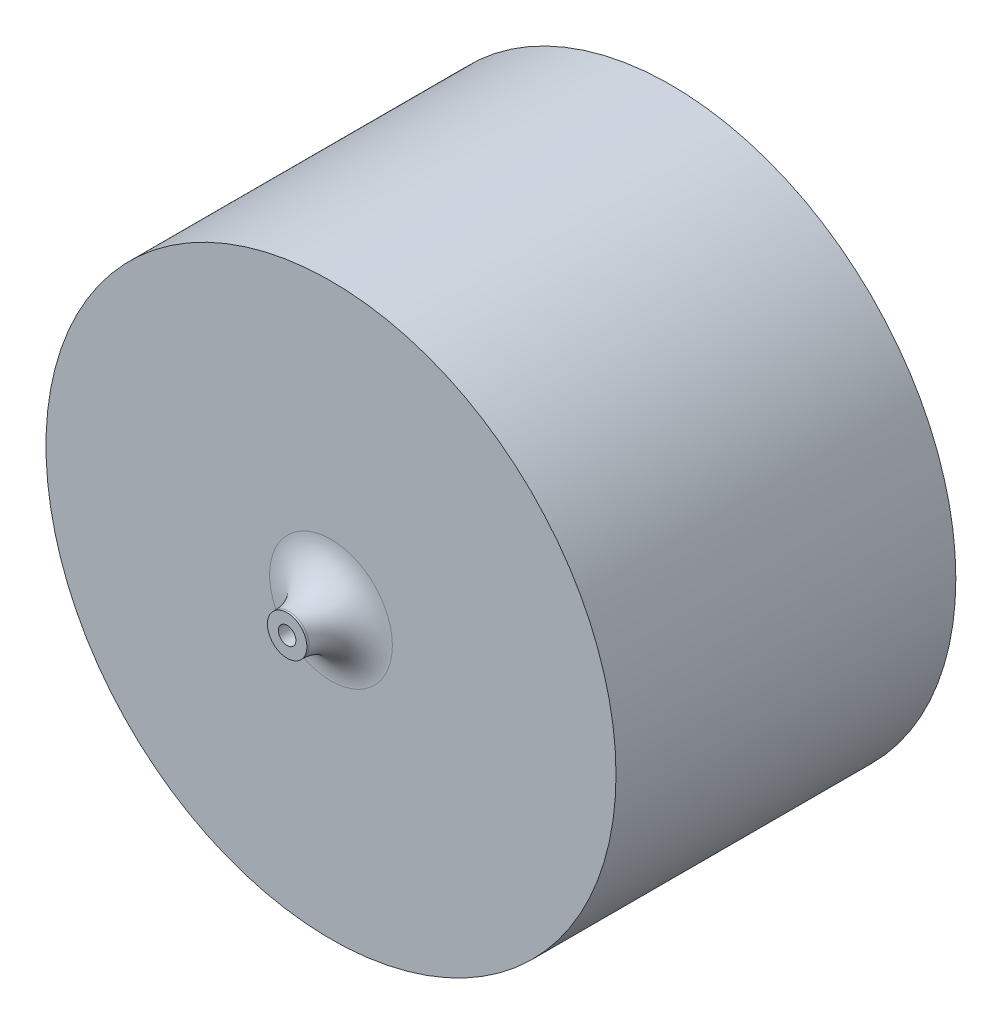
SolidWorks part; units mm, degrees
ref_plane "Front Plane" through (0, 0, 0) normal (0, 0, 1) x (1, 0, 0)
ref_plane "Top Plane" through (0, 0, 0) normal (0, 1, 0) x (1, 0, 0)
ref_plane "Right Plane" through (0, 0, 0) normal (1, 0, 0) x (0, 0, -1)
sketch "Sketch1" plane through (0, 0, 0) normal (1, 0, 0) x (0, 0, -1)
  line L0 (0, 0) -> (46.6464, 0) construction
  line L1 (6.35, 1.016) -> (6.35, 26.924)
  line L2 (44.45, 33.02) -> (5.08, 33.02)
  line L3 (5.08, 7.112) -> (5.08, 33.02)
  line L4 (44.45, 31.75) -> (11.176, 31.75)
  line L5 (0.254, 2.286) -> (0, 2.286)
  line L6 (6.35, 1.016) -> (0, 1.016)
  line L7 (0, 1.016) -> (0, 2.286)
  line L8 (44.45, 31.75) -> (44.45, 33.02)
  line L9 (5.08, 2.286) -> (5.08, 33.02) construction
  line L10 (5.08, 2.286) -> (0, 2.286) construction
  line L11 (44.45, 31.75) -> (6.35, 31.75) construction
  line L12 (6.35, 1.016) -> (6.35, 31.75) construction
  arc A0 (5.08, 7.112) -> (0.254, 2.286) centre (0.254, 7.112) cw
  arc A1 (11.176, 31.75) -> (6.35, 26.924) centre (11.176, 26.924) ccw
  dimension "D5" = 4.826
  dimension "D6" = 4.826
  dimension "D1" = 2.032
  dimension "D2" = 63.5
  dimension "D3" = 1.27
  dimension "D4" = 6.35
  dimension "D7" = 44.45
revolve "Revolve1" add sketch "Sketch1" angle 360 about L0
